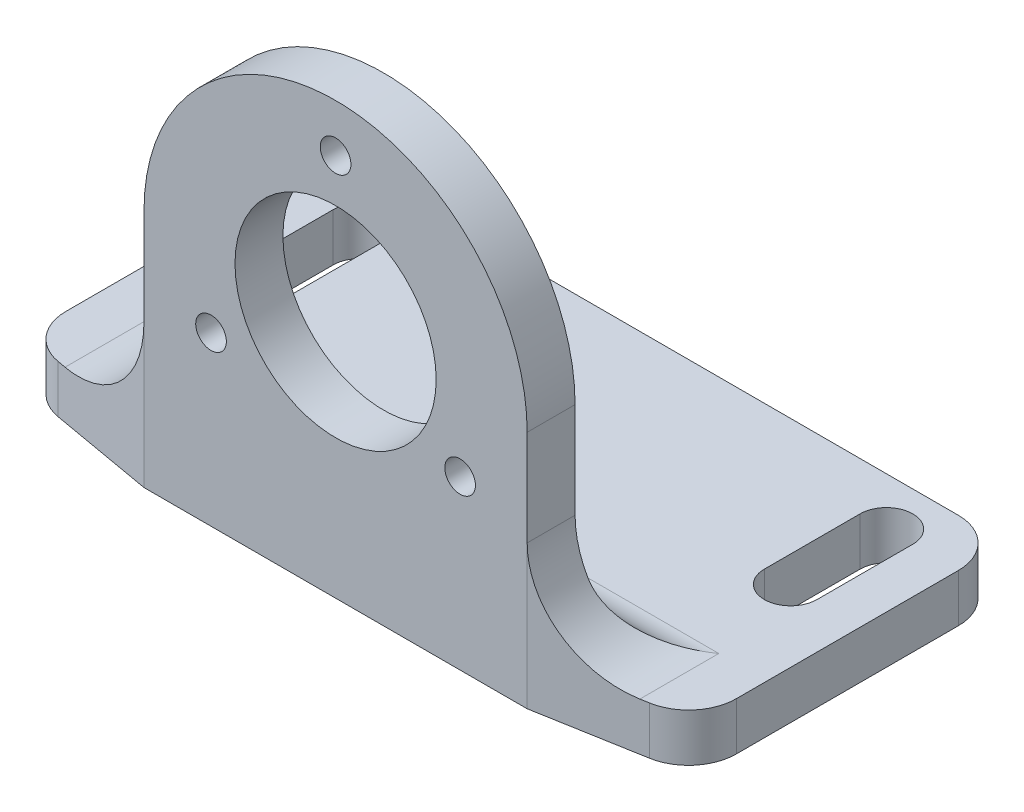
SolidWorks part; units mm, degrees
ref_plane "Front Plane" through (0, 0, 0) normal (0, 0, 1) x (1, 0, 0)
ref_plane "Top Plane" through (0, 0, 0) normal (0, 1, 0) x (1, 0, 0)
ref_plane "Right Plane" through (0, 0, 0) normal (1, 0, 0) x (0, 0, -1)
sketch "Sketch1" plane through (0, 0, 0) normal (0, 1, 0) x (1, 0, 0)
  line L1 (0, 0) -> (40, 0)
  line L2 (0, 0) -> (0, 30)
  line L3 (0, 30) -> (40, 30)
  line L4 (40, 0) -> (40, 30)
  dimension "D1" = 40
  dimension "D2" = 30
extrude "Boss-Extrude1" add sketch "Sketch1" along normal blind 5
sketch "Sketch2" plane through (0, 0, 0) normal (0, 0, 1) x (1, 0, 0)
  line L2 (0, 5) -> (0, 25)
  line L4 (40, 5) -> (40, 25)
  line L8 (0, 0) -> (40, 0)
  line L9 (40, 0) -> (40, 5)
  line L10 (40, 5) -> (0, 5)
  line L11 (0, 5) -> (0, 0)
  line L12 (0, 0) -> (40, 0)
  line L13 (40, 0) -> (40, 5)
  line L15 (0, 5) -> (0, 0)
  arc A0 (0, 25) -> (40, 25) centre (20, 25) cw
  dimension "D1" = 45
  dimension "D2" = 0
extrude "Boss-Extrude2" add sketch "Sketch2" along normal blind 5 contours A0 L4 L13 L12 L15 L2
sketch "Sketch4" plane through (0, 0, 5) normal (0, 0, 1) x (1, 0, 0)
  line L0 (20, 25) -> (20, 40.0111) construction
  line L1 (20, 40.0111) -> (7, 17.4944) construction
  line L2 (7, 17.4944) -> (33, 17.4944) construction
  line L3 (33, 17.4944) -> (20, 40.0111) construction
  line L4 (20, 25) -> (7, 17.4944) construction
  circle A0 centre (20, 25) radius 10.5
  circle A1 centre (20, 40.0111) radius 1.6
  circle A2 centre (7, 17.4944) radius 1.6
  circle A3 centre (33, 17.4944) radius 1.6
  dimension "D1" = 21
  dimension "D3" = 3.2
  dimension "D2" = 26
extrude "Cut-Extrude2" cut sketch "Sketch4" against normal blind 5
sketch "Sketch3" plane through (0, 5, 0) normal (0, 1, 0) x (1, 0, 0)
  line L0 (0, 20) -> (40, 20) construction
  line L3 (40, 20) -> (20, 30) construction
  line L4 (40, 30) -> (0, 30) construction
  line L5 (20, 30) -> (20, 20) construction
  circle A0 centre (7.5, 20) radius 2.65
  circle A1 centre (32.5, 20) radius 2.65
  point P2 (0, 0)
  dimension "D2" = 5.3
  dimension "D1" = 25
  dimension "D3" = 10
sketch "Sketch5" plane through (0, 5, 0) normal (0, 1, 0) x (1, 0, 0)
  line L1 (0, 0) -> (-15, 0)
  line L2 (0, 0) -> (0, 30)
  line L3 (0, 30) -> (-15, 30)
  line L4 (-15, 0) -> (-15, 30)
  line L9 (-7.5, 15) -> (-7.5, 25) construction
  line L10 (-10.25, 15) -> (-10.25, 25)
  line L11 (-4.75, 15) -> (-4.75, 25)
  line L12 (20, 30) -> (20, 0) construction
  line L13 (40, 30) -> (0, 30) construction
  line L14 (0, 0) -> (40, 0) construction
  line L15 (47.5, 15) -> (47.5, 25) construction
  line L16 (50.25, 15) -> (50.25, 25)
  line L17 (44.75, 15) -> (44.75, 25)
  line L18 (55, 0) -> (55, 30)
  line L19 (40, 30) -> (55, 30)
  line L20 (40, 0) -> (40, 30)
  line L21 (40, 0) -> (55, 0)
  arc A0 (-10.25, 15) -> (-4.75, 15) centre (-7.5, 15) ccw
  arc A1 (-4.75, 25) -> (-10.25, 25) centre (-7.5, 25) ccw
  arc A2 (50.25, 15) -> (44.75, 15) centre (47.5, 15) cw
  arc A3 (44.75, 25) -> (50.25, 25) centre (47.5, 25) cw
  point P7 (47.5, 20)
  point P15 (-7.5, 20)
  point P22 (-7.5, 30)
  point P33 (0, 0)
  point P34 (-7.5, 18.3814)
  dimension "D2" = 2.75
  dimension "D1" = 15
  dimension "D3" = 10
extrude "Boss-Extrude3" add sketch "Sketch5" against normal up to vertex (5 mm away) up to point (0, 0, -30)
chamfer "Chamfer1" distance 5 angle 80 1 edges at (0, 2.5, 0) first distance on face at (0, 11, 2)
chamfer "Chamfer2" distance 5 angle 80 1 edges at (40, 2.5, 0) first distance on face at (40, 11, 2)
fillet "Fillet1" radius 10 2 edges at (0, 5, 2.5) (40, 5, 2.5)
fillet "Fillet2" radius 5 4 edges at (55, 2.5, 2.3551) (-15, 2.5, 2.3551) (-15, 2.5, -30) (55, 2.5, -30)
fillet "Fillet4" radius 5 1 edges at (20, 5, 0)
sketch "Sketch6" plane through (0, 0, 0) normal (0, 0, -1) x (-1, 0, 0)
  line L1 (-25.611, 5) -> (-14.389, 5)
  line L4 (10, 5) -> (-50, 5) construction
  line L5 (-50, 5) -> (10, 5) construction
  arc A1 (-40, 25) -> (0, 25) centre (-20, 25) cw
  arc A2 (-40, 25) -> (-25.611, 5) centre (-20, 24.2129) ccw
  arc A3 (0, 25) -> (-40, 25) centre (-20, 25) ccw construction
  arc A4 (-14.389, 5) -> (0, 25) centre (-20, 24.2129) ccw
  point P2 (0, 0)
  point P4 (-20, 5)
  point P12 (0, 0)
  point P13 (-14.3573, 5)
extrude "Cut-Extrude3" cut sketch "Sketch6" along normal through all
